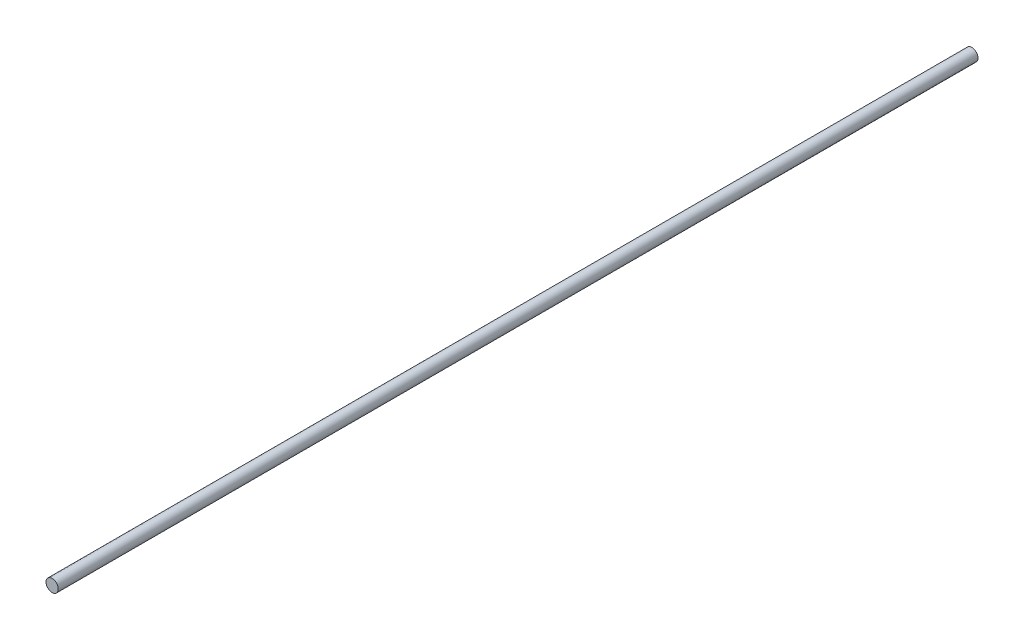
SolidWorks part; units mm, degrees
note: '?' marks a value the reader was unsure of.
material "Ст 3 ГОСТ 380-88"
ref_plane "Спереди" through (0, 0, 0) normal (0, 0, 1) x (1, 0, 0)
ref_plane "Сверху" through (0, 0, 0) normal (0, 1, 0) x (1, 0, 0)
ref_plane "Справа" through (0, 0, 0) normal (1, 0, 0) x (0, 0, -1)
sketch "Эскиз1" plane through (0, 0, 0) normal (0, 0, 1) x (1, 0, 0)
  circle A0 centre (0, 0) radius 10
  circle A1 centre (0, 0) radius 50 construction
  point P5 (0, 0)
  dimension "D1" = 20
  dimension "D2" = 100
extrude "Бобышка-Вытянуть1" add sketch "Эскиз1" along normal blind 1480 and the other way blind 20
ref_axis "Axis1" through (0, 0, -75) along (0, 0, 1)?
ref_plane "Plane1" through (0, 0, 730) normal (0, 0, 1) x (1, 0, 0)
